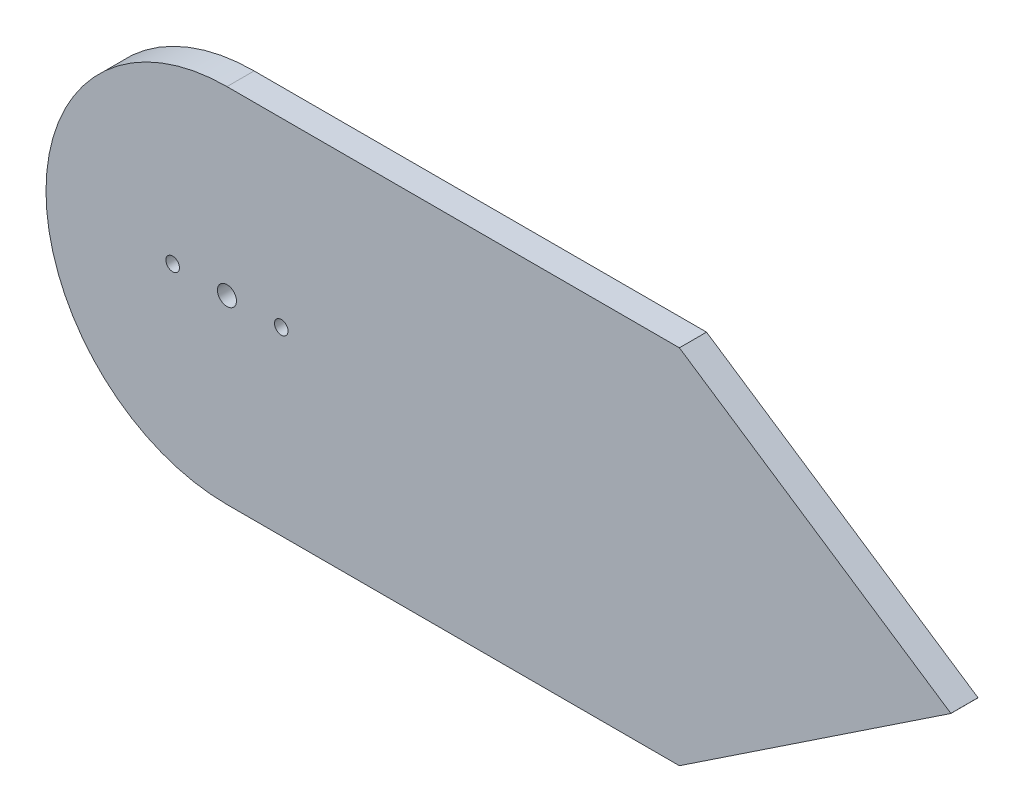
SolidWorks part; units mm, degrees
material "Acrylic (Medium-high impact)"
ref_plane "Front Plane" through (0, 0, 0) normal (0, 0, 1) x (1, 0, 0)
ref_plane "Top Plane" through (0, 0, 0) normal (0, 1, 0) x (1, 0, 0)
ref_plane "Right Plane" through (0, 0, 0) normal (1, 0, 0) x (0, 0, -1)
sketch "Sketch1" plane through (0, 0, 0) normal (0, 1, 0) x (1, 0, 0)
  line L0 (50, -20) -> (0, -20)
  line L2 (0, 20) -> (50, 20)
  line L3 (50, 20) -> (80, 0.0108)
  line L4 (80, 0) -> (50, -20)
  line L5 (80, 0) -> (80, 0.0108)
  arc A0 (0, 20) -> (0, -20) centre (0, 0) ccw
  dimension "D1" = 40
  dimension "D3" = 50
  dimension "D2" = 80
  dimension "D4" = 50
extrude "Boss-Extrude1" add sketch "Sketch1" along normal blind 3 contours L2 L3 L5 L4 L0 A0
move or copy body "Body-Move/Copy1" bodies to move or copy 101 copy no rotation origin (0, 0, 0) rotation axis (1, 0, 0) rotation angle 90
sketch "Sketch8" plane through (0, 0, 3) normal (0, 0, 1) x (1, 0, 0)
  circle A0 centre (0, 0) radius 1.05
  circle A2 centre (0, 0) radius 1.05
  circle A3 centre (6, -0.0326) radius 0.75
  circle A4 centre (0, 0) radius 1.05
  circle A6 centre (0, 0) radius 1.05
  circle A7 centre (-5.9999, 0.0279) radius 0.75
  point P17 (0, 0)
  dimension "D1" = 2.1
  dimension "D3" = 6
  dimension "D5" = 1.5
  dimension "D6" = 1.5
  dimension "D2" = 6
  dimension "D4" = 4
extrude "Cut-Extrude2" cut sketch "Sketch8" against normal up to next contours A0 | A7 | A3 region at (0, 0, 3) region at (-5.9999, 0.0279, 3)
move or copy body "Body-Move/Copy4" bodies to move or copy 111 copy no translate (0, 0, -3)
sketch "Sketch9" plane through (0, 0, 0) normal (0, 0, 1) x (1, 0, 0)
  point P0 (80, 0)
